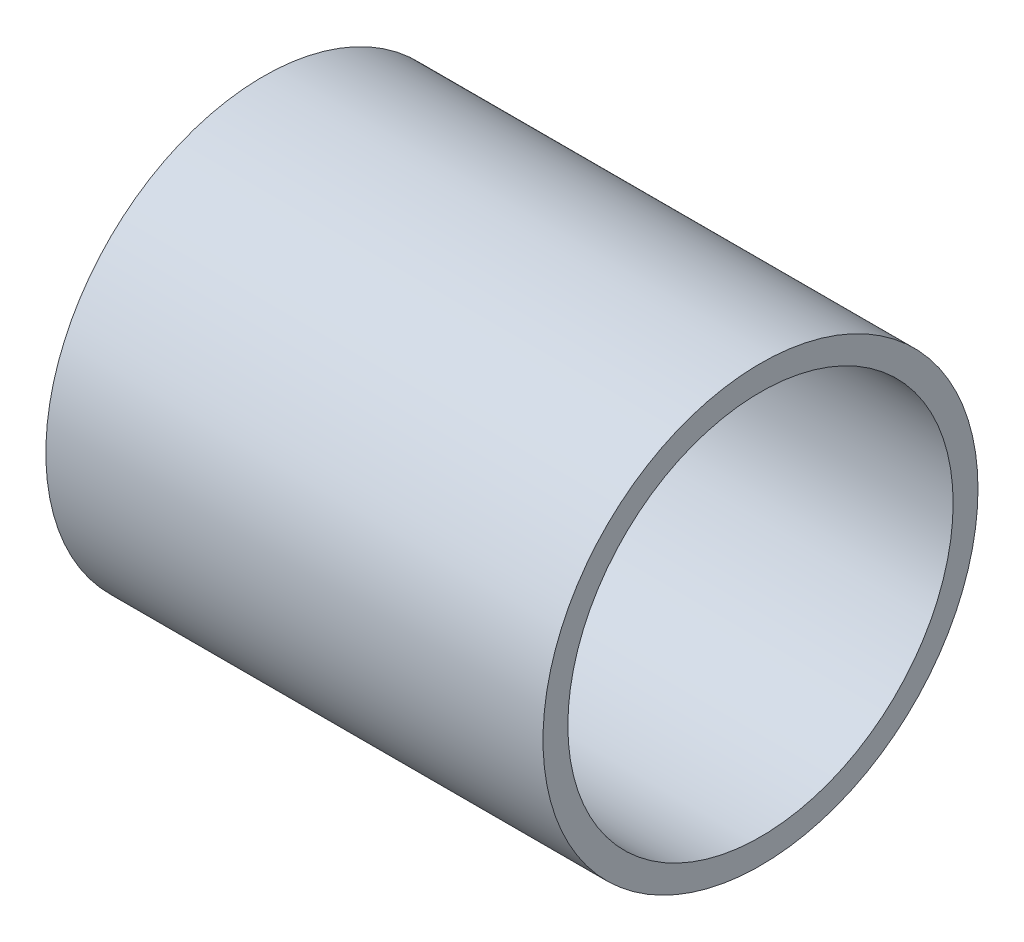
SolidWorks part; units mm, degrees
ref_plane "Front Plane" through (0, 0, 0) normal (0, 0, 1) x (1, 0, 0)
ref_plane "Top Plane" through (0, 0, 0) normal (0, 1, 0) x (1, 0, 0)
ref_plane "Right Plane" through (0, 0, 0) normal (1, 0, 0) x (0, 0, -1)
sketch "Sketch2" plane through (0, 0, 0) normal (0, 0, 1) x (1, 0, 0)
  line L0 (-160, -120.5) -> (-260, 120.5) construction
  line L1 (-260, 120.5) -> (260, 120.5) construction
  line L2 (260, 120.5) -> (160, -120.5) construction
  line L3 (160, -120.5) -> (-160, -120.5) construction
  line L4 (0, 120.5) -> (0, -120.5) construction
  point P6 (-160, -147.0895)
  point P8 (0, 0)
  dimension "D1" = 520
  dimension "D2" = 320
  dimension "D3" = 241
sketch "Sketch4" plane through (0, 0, 0) normal (1, 0, 0) x (0, 0, -1)
  line L0 (0, 120.5) -> (0, -120.5) construction
  line L2 (-10, -110.5) -> (10, -110.5) construction
  line L3 (-10, -110.5) -> (-10, -130.5) construction
  line L4 (-10, -130.5) -> (10, -130.5) construction
  line L5 (10, -110.5) -> (10, -130.5) construction
  line L6 (-10, -110.5) -> (10, -130.5) construction
  line L7 (-10, -130.5) -> (10, -110.5) construction
  circle A0 centre (0, -120.5) radius 15.5
  circle A1 centre (0, -120.5) radius 17.5
  dimension "D1" = 2
  dimension "D2" = 35
  dimension "D3" = 20
extrude "Boss-Extrude1" add sketch "Sketch4" along normal blind 40 from offset 100
sketch "Sketch5" plane through (0, 0, 0) normal (0, 1, 0) x (1, 0, 0)
  line L0 (311.7879, 140.4045) -> (371.7879, 140.4045)
  line L1 (291.7879, -227.8955) -> (311.7879, -227.8955)
  line L2 (291.7879, -227.8955) -> (291.7879, 210.4045)
  line L3 (291.7879, 210.4045) -> (311.7879, 210.4045)
  line L4 (311.7879, -227.8955) -> (311.7879, 140.4045)
  line L5 (371.7879, -236.7452) -> (391.7879, -236.7452)
  line L6 (371.7879, -236.7452) -> (371.7879, 140.4045)
  line L7 (371.7879, 210.4045) -> (391.7879, 210.4045)
  line L8 (391.7879, -236.7452) -> (391.7879, 210.4045)
  line L9 (311.7879, 160.4045) -> (371.7879, 160.4045)
  line L10 (341.7879, 140.4045) -> (341.7879, 160.4045) construction
  line L11 (311.7879, 160.4045) -> (311.7879, 210.4045)
  line L12 (371.7879, 160.4045) -> (371.7879, 210.4045)
  line L13 (214.5805, 190.4045) -> (214.5805, 210.4045) construction
  line L14 (291.7879, 210.4045) -> (137.373, 210.4045)
  line L15 (291.7879, 210.4045) -> (291.7879, 190.4045)
  line L16 (291.7879, 190.4045) -> (137.373, 190.4045)
  line L18 (100, 17.5) -> (137.373, 17.5)
  line L19 (100, 17.5) -> (100, 210.4045)
  line L20 (100, 210.4045) -> (137.373, 210.4045)
  line L21 (137.373, 17.5) -> (137.373, 210.4045)
  line L22 (291.7879, 108.2576) -> (147.8251, 108.2576)
  line L23 (291.7879, 108.2576) -> (291.7879, 122.1154)
  line L24 (291.7879, 122.1154) -> (147.8251, 122.1154)
  dimension "D1" = 20
  dimension "D2" = 60
  dimension "D3" = 368.3
  dimension "D4" = 50
  dimension "D5" = 438.3
